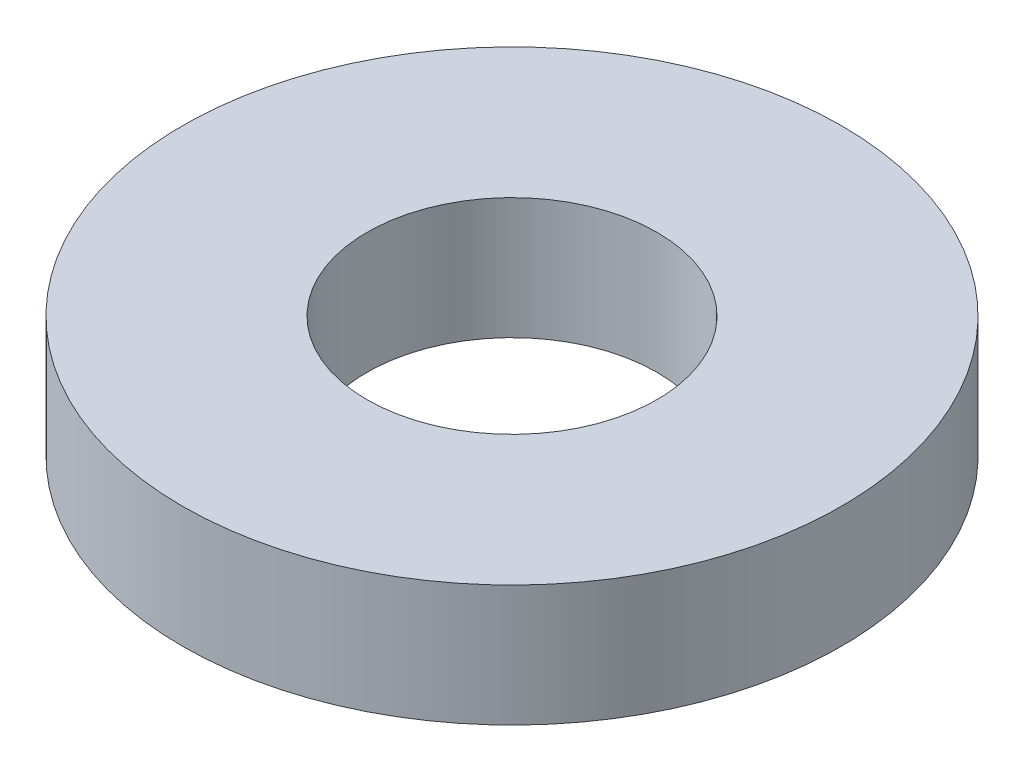
SolidWorks part; units mm, degrees
ref_plane "Front Plane" through (0, 0, 0) normal (0, 0, 1) x (1, 0, 0)
ref_plane "Top Plane" through (0, 0, 0) normal (0, 1, 0) x (1, 0, 0)
ref_plane "Right Plane" through (0, 0, 0) normal (1, 0, 0) x (0, 0, -1)
sketch "Sketch1" plane through (0, 0, 0) normal (0, 1, 0) x (1, 0, 0)
  circle A0 centre (0, 0) radius 62.5
  dimension "FLANGE_OD" = 125
extrude "Boss-Extrude1" add sketch "Sketch1" along normal blind 23
sketch "Sketch2" plane through (0, 0, 0) normal (0, 1, 0) x (1, 0, 0)
  circle A0 centre (0, 0) radius 27.5
  dimension "BORE_D" = 55
extrude "Cut-Extrude1" cut sketch "Sketch2" along normal through all
sketch "Sketch3" plane through (0, 23, 0) normal (0, 1, 0) x (1, 0, 0)
  circle A0 centre (0, 0) radius 21.0767 construction
  circle A1 centre (-21.0767, 0) radius 3.0904
  dimension "BOLT_D" = 6.1808
  dimension "BOLT_PCD" = 42.1533
extrude "Cut-Extrude2" cut sketch "Sketch3" against normal blind 15.9312 rebuild error yes
pattern_circular "CirPattern1" count 8 over 360 rebuild error yes
